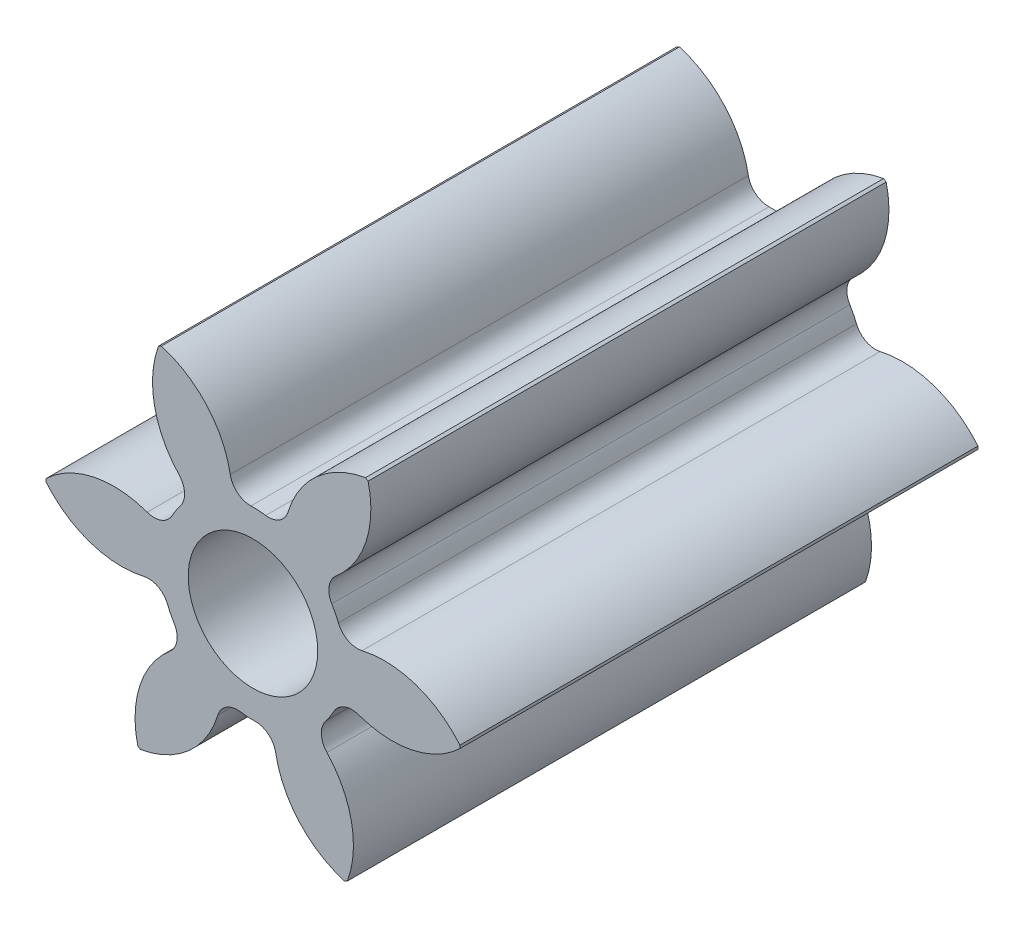
SolidWorks part; units mm, degrees
ref_plane "Front" through (0, 0, 0) normal (0, 0, 1) x (1, 0, 0)
ref_plane "Top" through (0, 0, 0) normal (0, 1, 0) x (1, 0, 0)
ref_plane "Right" through (0, 0, 0) normal (1, 0, 0) x (0, 0, -1)
sketch "Sketch3" plane through (0, 0, 0) normal (0, 0, 1) x (1, 0, 0)
  circle A0 centre (0, 0) radius 10.16
  dimension "od" = 20.32
extrude "gearBody" add sketch "Sketch3" along normal blind 25.4
sketch "Sketch2" plane through (0, 0, 0) normal (0, 0, 1) x (1, 0, 0)
  line L0 (0, 0) -> (6.8157, 2.8232) construction
  line L1 (3.4575, -10.8399) -> (0, 0) construction
  line L2 (0, 0) -> (36.3143, 0) construction
  line L3 (7.3626, -1.964) -> (4.7199, -5.9822) construction
  line L5 (6.0412, -3.9731) -> (0, 0) construction
  line L7 (0, 0) -> (7.3773, 0) construction
  arc A0 (7.1048, -1.9864) -> (4.6384, -5.7367) centre (0, 0) ccw construction
  arc A1 (10.1381, -0.6664) -> (4.628, -9.0447) centre (0, 0) ccw construction
  arc A2 (7.3626, -1.964) -> (4.7199, -5.9822) centre (0, 0) ccw construction
  arc A3 (3.566, -2.7793) -> (3.9646, -2.1733) centre (0, 0) ccw
  arc A4 (3.4575, -10.8399) -> (3.6251, -4.0834) centre (0.1078, -7.3765) ccw
  arc A5 (3.4575, -10.8399) -> (11.3227, 1.1195) centre (0, 0) ccw
  arc A6 (11.3227, 1.1195) -> (5.1854, -1.7109) centre (6.8157, 2.8232) cw
  arc A7 (3.9646, -2.1733) -> (5.1854, -1.7109) centre (4.8455, -2.6562) cw
  arc A8 (3.6251, -4.0834) -> (3.566, -2.7793) centre (4.3584, -3.3969) cw
  point P6 (11.3227, 1.1195)
  point P22 (3.4575, -10.8399)
  dimension "baseDia" = 14.7546
  dimension "od" = 20.32
  dimension "pd" = 15.24
  dimension "rd" = 9.0424
  dimension "rFillet" = 1.0046
  dimension "pointX" = 11.3227
  dimension "pointY" = 1.1195
  dimension "CTT" = 4.0183
  dimension "flankCenterAngle" = 22.5
extrude "toothCut" cut sketch "Sketch2" along normal through all
pattern_circular "CirPattern1" count 6 over 360 about axis through (0, 0, 25.4) along (0, 0, -1) of "toothCut"
ref_axis "toothSpace" through (0, 0, 0) along (0.8355, -0.5495, 0)
ref_axis "Axis2" through (4.5601, -9.0792, 0) along (-0.4488, 0.8936, 0)
sketch "hub1Dia" plane through (0, 0, 0) normal (0, 0, -1) x (-1, 0, 0)
  circle A0 centre (0, 0) radius 12.7
  dimension "hub1Dia" = 25.4
sketch "hub2Dia" plane through (0, 0, 25.4) normal (0, 0, 1) x (1, 0, 0)
  circle A0 centre (0, 0) radius 12.7
  dimension "hub2dia" = 25.4
sketch "boreDia" plane through (0, 0, 0) normal (0, 0, 1) x (1, 0, 0)
  circle A0 centre (0, 0) radius 3.175
  dimension "boreDia" = 6.35
extrude "bore" cut sketch "boreDia" against normal mid plane 25400
sketch "kwy1sketch" plane through (0, 0, 0) normal (0, 0, 1) x (1, 0, 0)
  line L0 (-2.3856, 3.2042) -> (0, 0) construction
  line L1 (27.2513, -15.3359) -> (6.8778, -30.5044)
  line L2 (6.8778, -30.5044) -> (-12.0828, -5.0376)
  line L3 (27.2513, -15.3359) -> (8.2907, 10.1309)
  line L4 (-12.0828, -5.0376) -> (0, 0)
  line L5 (0, 0) -> (8.2907, 10.1309)
  line L6 (0, 0) -> (3.7775, -2.4843) construction
  line L7 (17.0645, -22.9201) -> (0, 0) construction
  arc A7 (3.566, -2.7793) -> (3.9646, -2.1733) centre (0, 0) ccw construction
  point P9 (17.0645, -22.9201)
  point P13 (-0.3979, 0.5345)
  dimension "kwy1width" = 25.4
  dimension "kwy1depth" = 28.575
  dimension "kwy1angle" = 20
  dimension "kwy1Depth2" = 31.75
sketch "kwy2sketch" plane through (0, 0, 0) normal (0, 0, 1) x (1, 0, 0)
  line L0 (3.7775, -2.4843) -> (0, 0) construction
  line L1 (0, 0) -> (-2.7313, 0.4) construction
  line L2 (30.1137, 8.4254) -> (26.4332, -16.7065)
  line L3 (26.4332, -16.7065) -> (-4.9817, -12.1059)
  line L4 (30.1137, 8.4254) -> (-1.3013, 13.026)
  line L5 (-4.9817, -12.1059) -> (0, 0)
  line L6 (0, 0) -> (-1.3013, 13.026)
  arc A2 (3.566, -2.7793) -> (3.9646, -2.1733) centre (0, 0) ccw construction
  point P10 (28.2734, -4.1405)
  dimension "kwy2angle" = 25
  dimension "kwy2Width" = 25.4
  dimension "kwy2depth" = 28.575
  dimension "kwy2Depth2" = 31.75
sketch "kwy3sketch" plane through (0, 0, 0) normal (0, 0, 1) x (1, 0, 0)
  line L0 (3.7775, -2.4843) -> (0, 0) construction
  line L1 (0, 0) -> (-1.6019, -1.1926) construction
  line L2 (15.3359, 27.2513) -> (30.5044, 6.8778)
  line L3 (30.5044, 6.8778) -> (5.0376, -12.0828)
  line L4 (15.3359, 27.2513) -> (-10.1309, 8.2907)
  line L5 (5.0376, -12.0828) -> (0, 0)
  line L6 (-10.1309, 8.2907) -> (0, 0)
  point P10 (22.9201, 17.0645)
  dimension "kwy3angle" = 70
  dimension "kwy3depth" = 28.575
  dimension "kwy3width" = 25.4
  dimension "kwy3Depth2" = 31.75
sketch "kwy4sketch" plane through (0, 0, 0) normal (0, 0, 1) x (1, 0, 0)
  line L0 (3.7775, -2.4843) -> (0, 0) construction
  line L1 (0, 0) -> (-0.2263, -1.545) construction
  line L2 (16.7065, 26.4332) -> (-8.4254, 30.1137)
  line L3 (-8.4254, 30.1137) -> (-13.026, -1.3013)
  line L4 (-13.026, -1.3013) -> (0, 0)
  line L5 (12.1059, -4.9817) -> (0, 0)
  line L6 (16.7065, 26.4332) -> (12.1059, -4.9817)
  point P15 (4.1405, 28.2734)
  dimension "kwy4angle" = 115
  dimension "kwy4depth" = 28.575
  dimension "kwy4width" = 25.4
  dimension "kwy4Depth2" = 31.75
sketch "kwy5sketch" plane through (0, 0, 0) normal (0, 0, 1) x (1, 0, 0)
  line L0 (3.7775, -2.4843) -> (0, 0) construction
  line L1 (0, 0) -> (0.8009, -1.0757) construction
  line L2 (-6.8778, 30.5044) -> (-27.2513, 15.3359)
  line L3 (-27.2513, 15.3359) -> (-8.2907, -10.1309)
  line L4 (-6.8778, 30.5044) -> (12.0828, 5.0376)
  line L5 (-8.2907, -10.1309) -> (0, 0)
  line L6 (12.0828, 5.0376) -> (0, 0)
  point P10 (-17.0645, 22.9201)
  dimension "kwy5width" = 25.4
  dimension "kwy5depth" = 28.575
  dimension "kwy5angle" = 160
  dimension "kwy5Depth2" = 31.75
sketch "kwy6sketch" plane through (0, 0, 0) normal (0, 0, 1) x (1, 0, 0)
  line L0 (3.7775, -2.4843) -> (0, 0) construction
  line L1 (0, 0) -> (1.3259, -0.1942) construction
  line L2 (-26.4332, 16.7065) -> (-30.1137, -8.4254)
  line L3 (-30.1137, -8.4254) -> (1.3013, -13.026)
  line L4 (-26.4332, 16.7065) -> (4.9817, 12.1059)
  line L5 (1.3013, -13.026) -> (0, 0)
  line L6 (4.9817, 12.1059) -> (0, 0)
  point P10 (-28.2734, 4.1405)
  dimension "kwy6angle" = 205
  dimension "kwy6width" = 25.4
  dimension "kwy6depth" = 28.575
  dimension "kwy6Depth2" = 31.75
sketch "kwy7sketch" plane through (0, 0, 0) normal (0, 0, 1) x (1, 0, 0)
  line L0 (3.7775, -2.4843) -> (0, 0) construction
  line L1 (0, 0) -> (1.2042, 0.8965) construction
  line L2 (-30.5044, -6.8778) -> (-15.3359, -27.2513)
  line L3 (-30.5044, -6.8778) -> (-5.0376, 12.0828)
  line L4 (-15.3359, -27.2513) -> (10.1309, -8.2907)
  line L5 (-5.0376, 12.0828) -> (0, 0)
  line L6 (10.1309, -8.2907) -> (0, 0)
  point P10 (-22.9201, -17.0645)
  dimension "kwy7angle" = 70
  dimension "kwy7width" = 25.4
  dimension "kwy7depth" = 28.575
  dimension "kwy7angle1" = 250
  dimension "kwy7Depth2" = 31.75
sketch "kwy8sketch" plane through (0, 0, 0) normal (0, 0, 1) x (1, 0, 0)
  line L0 (3.7775, -2.4843) -> (0, 0) construction
  line L1 (0, 0) -> (0.1933, 1.3197) construction
  line L2 (-16.7065, -26.4332) -> (8.4254, -30.1137)
  line L3 (8.4254, -30.1137) -> (13.026, 1.3013)
  line L4 (-16.7065, -26.4332) -> (-12.1059, 4.9817)
  line L5 (13.026, 1.3013) -> (0, 0)
  line L6 (-12.1059, 4.9817) -> (0, 0)
  point P10 (-4.1405, -28.2734)
  dimension "kwy8angle" = 295
  dimension "kwy8width" = 25.4
  dimension "kwy8depth" = 28.575
  dimension "kwy8Depth2" = 31.75
sketch "centerLine" plane through (0, 0, 0) normal (0, 1, 0) x (1, 0, 0)
  line L0 (0, 36.4807) -> (0, -59.6309) construction
ref_plane "CB1plane" through (0, 0, 0) normal (0, 0, -1) x (-1, 0, 0)
sketch "CB1diameter" plane through (0, 0, 0) normal (0, 0, -1) x (-1, 0, 0)
  circle A0 centre (0, 0) radius 12.7
  dimension "CB1diameter" = 25.4
ref_plane "CB2plane" through (0, 0, 25.4) normal (0, 0, 1) x (1, 0, 0)
sketch "CB2diameter" plane through (0, 0, 25.4) normal (0, 0, 1) x (1, 0, 0)
  circle A0 centre (0, 0) radius 12.7
  dimension "CB2diameter" = 25.4
ref_axis "Axis1" through (0, 0, 50) along (0, 0, -1)
sketch3d "3DSketch1" plane through (0, 0, 0) normal (0, 0, 1) x (1, 0, 0)
